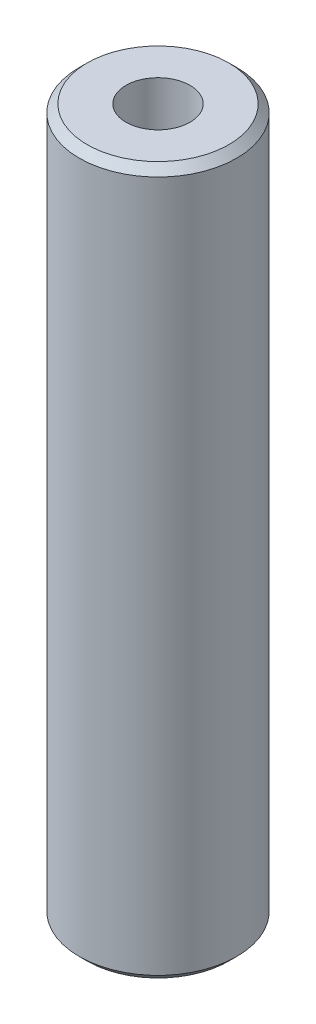
SolidWorks part; units mm, degrees
ref_plane "Front Plane" through (0, 0, 0) normal (0, 0, 1) x (1, 0, 0)
ref_plane "Top Plane" through (0, 0, 0) normal (0, 1, 0) x (1, 0, 0)
ref_plane "Right Plane" through (0, 0, 0) normal (1, 0, 0) x (0, 0, -1)
sketch "Sketch1" plane through (0, 0, 0) normal (0, 1, 0) x (1, 0, 0)
  circle A0 centre (0, 0) radius 60
  dimension "SHAFT_OD" = 120
extrude "Boss-Extrude1" add sketch "Sketch1" along normal blind 539.2476
sketch "Sketch2" plane through (0, 0, 0) normal (0, 1, 0) x (1, 0, 0)
  circle A0 centre (0, 0) radius 24.4001
  dimension "BORE_D" = 48.8001
extrude "Cut-Extrude1" cut sketch "Sketch2" along normal through all
chamfer "Chamfer1" distance 5.9719 angle 45 2 edges at (0, 539.2476, 60) (0, 0, 60)
